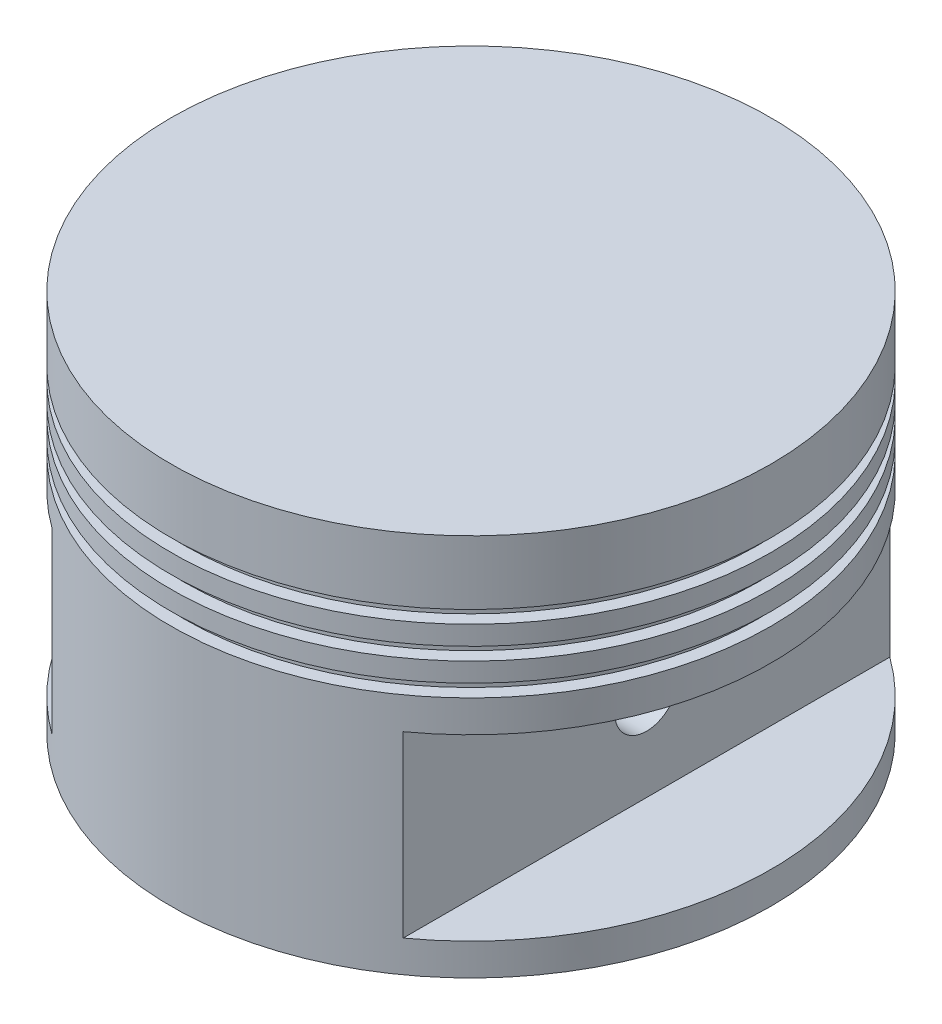
SolidWorks part; units mm, degrees
ref_plane "Front Plane" through (0, 0, 0) normal (0, 0, 1) x (1, 0, 0)
ref_plane "Top Plane" through (0, 0, 0) normal (0, 1, 0) x (1, 0, 0)
ref_plane "Right Plane" through (0, 0, 0) normal (1, 0, 0) x (0, 0, -1)
sketch "Sketch1" plane through (0, 0, 0) normal (0, 0, 1) x (1, 0, 0)
  line L0 (0, 0) -> (0, -60)
  line L1 (0, 0) -> (-47, 0)
  line L2 (-47, -12) -> (-47, -15)
  line L3 (0, -60) -> (-47, -60)
  line L4 (-47, 0) -> (-47, -10)
  line L5 (-45, -15) -> (-45, -17)
  line L6 (-45, -20) -> (-45, -22)
  line L7 (-45, -10) -> (-47, -10)
  line L8 (-45, -10) -> (-45, -12)
  line L9 (-45, -12) -> (-47, -12)
  line L11 (-45, -15) -> (-47, -15)
  line L12 (-45, -15) -> (-45, -17)
  line L13 (-45, -17) -> (-47, -17)
  line L14 (-47, -17) -> (-47, -20)
  line L15 (-45, -20) -> (-47, -20)
  line L16 (-47, -22) -> (-47, -60)
  line L17 (-45, -22) -> (-47, -22)
  dimension "D1" = 3
  dimension "D2" = 2
  dimension "D3" = 2
  dimension "D4" = 60
  dimension "D5" = 10
  dimension "D6" = 3
  dimension "D7" = 2
  dimension "D8" = 2
  dimension "D9" = 47
  dimension "D10" = 0
  dimension "D11" = 0
revolve "Revolve1" add sketch "Sketch1" angle 360 about L0 region at (-23.4038, -30.0598, 0)
sketch "Sketch3" plane through (0, 0, 0) normal (0, 0, 1) x (1, 0, 0)
  line L0 (47, -22) -> (-47, -22) construction
  line L1 (-47.5, -27) -> (47.5, -27)
  line L3 (-47.5, -55) -> (47.5, -55)
  line L4 (47.5, -27) -> (27.5, -27)
  line L5 (-47, -60) -> (47, -60) construction
  line L8 (47.5, -27) -> (47.5, -55)
  line L9 (-27.5, -27) -> (27.5, -27)
  line L10 (-27.5, -27) -> (-27.5, -55)
  line L11 (-27.5, -55) -> (27.5, -55)
  line L12 (27.5, -27) -> (27.5, -55)
  line L13 (47.5, -55) -> (27.5, -55)
  line L14 (27.5, -27) -> (27.5, -55)
  line L15 (-27.5, -55) -> (-47.5, -55)
  line L16 (-27.5, -55) -> (-27.5, -27)
  line L17 (-27.5, -27) -> (-47.5, -27)
  line L18 (-47.5, -55) -> (-47.5, -27)
  dimension "D1" = 5
  dimension "D2" = 5
  dimension "D3" = 28
  dimension "D4" = 20
  dimension "D5" = 20
  dimension "D6" = 27.5
  dimension "D7" = 27.5
extrude "Cut-Extrude1" cut sketch "Sketch3" against normal through all both and the other way through all contours L10 L1 L18 L3 | L1 L12 L3 L8 region at (-37.5, -41, 0) region at (37.5, -41, 0)
shell "Shell1" thickness 10 removed face at (-47, -60, 0)
sketch "Sketch4" plane through (0, 0, 0) normal (0, 1, 0) x (1, 0, 0)
  circle A0 centre (0, 0) radius 41
  dimension "D1" = 82
extrude "Boss-Extrude2" add sketch "Sketch4" against normal blind 18
sketch "Sketch5" plane through (27.5, 0, 0) normal (1, 0, 0) x (0, 0, -1)
  line L2 (38.115, -27) -> (-38.115, -27) construction
  line L3 (38.115, -55) -> (38.115, -27) construction
  circle A0 centre (0, -41) radius 5
  dimension "D1" = 10
  dimension "D2" = 14
  dimension "D3" = 38.115
extrude "Cut-Extrude2" cut sketch "Sketch5" against normal through all both and the other way through all
